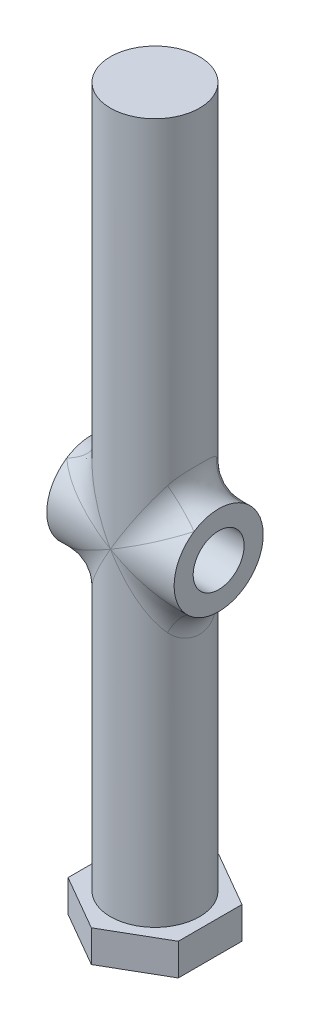
SolidWorks part; units mm, degrees
material "AISI 1020 Steel, Cold Rolled"
ref_plane "Front Plane" through (0, 0, 0) normal (0, 0, 1) x (1, 0, 0)
ref_plane "Top Plane" through (0, 0, 0) normal (0, 1, 0) x (1, 0, 0)
ref_plane "Right Plane" through (0, 0, 0) normal (1, 0, 0) x (0, 0, -1)
sketch "Sketch1" plane through (0, 0, 0) normal (0, 1, 0) x (1, 0, 0)
  line L1 (0, 10) -> (-8.6603, 5)
  line L2 (-8.6603, 5) -> (-8.6603, -5)
  line L3 (-8.6603, -5) -> (0, -10)
  line L4 (0, -10) -> (8.6603, -5)
  line L5 (8.6603, -5) -> (8.6603, 5)
  line L6 (8.6603, 5) -> (0, 10)
  circle A0 centre (0, 0) radius 10
  circle A1 centre (0, 0) radius 8.6603 construction
  dimension "D1" = 20
extrude "Boss-Extrude1" add sketch "Sketch1" along normal blind 5 contours L5 L6 L1 L2 L3 L4 region at (0, 0, 0)
sketch "Sketch2" plane through (0, 5, 0) normal (0, 1, 0) x (1, 0, 0)
  circle A0 centre (0, 0) radius 7
  dimension "D1" = 14
extrude "Boss-Extrude2" add sketch "Sketch2" along normal blind 110
sketch "Sketch3" plane through (0, 0, 0) normal (1, 0, 0) x (0, 0, -1)
  line L0 (7, 5) -> (7, 115) construction
  circle A0 centre (0, 55) radius 4
  dimension "D2" = 8
  dimension "D1" = 55
  dimension "D3" = 7
extrude "Cut-Extrude1" cut sketch "Sketch3" against normal through all both and the other way through all
sketch "Sketch4" plane through (0, 0, 0) normal (1, 0, 0) x (0, 0, -1)
  circle A0 centre (0, 55) radius 4
  circle A1 centre (0, 55) radius 7
  dimension "D1" = 14
extrude "Boss-Extrude3" add sketch "Sketch4" along normal mid plane 20
fillet "Fillet1" radius 5 4 edges at (7, 62, 0) (7, 48, 0) (-7, 48, 0) (-7, 62, 0)
